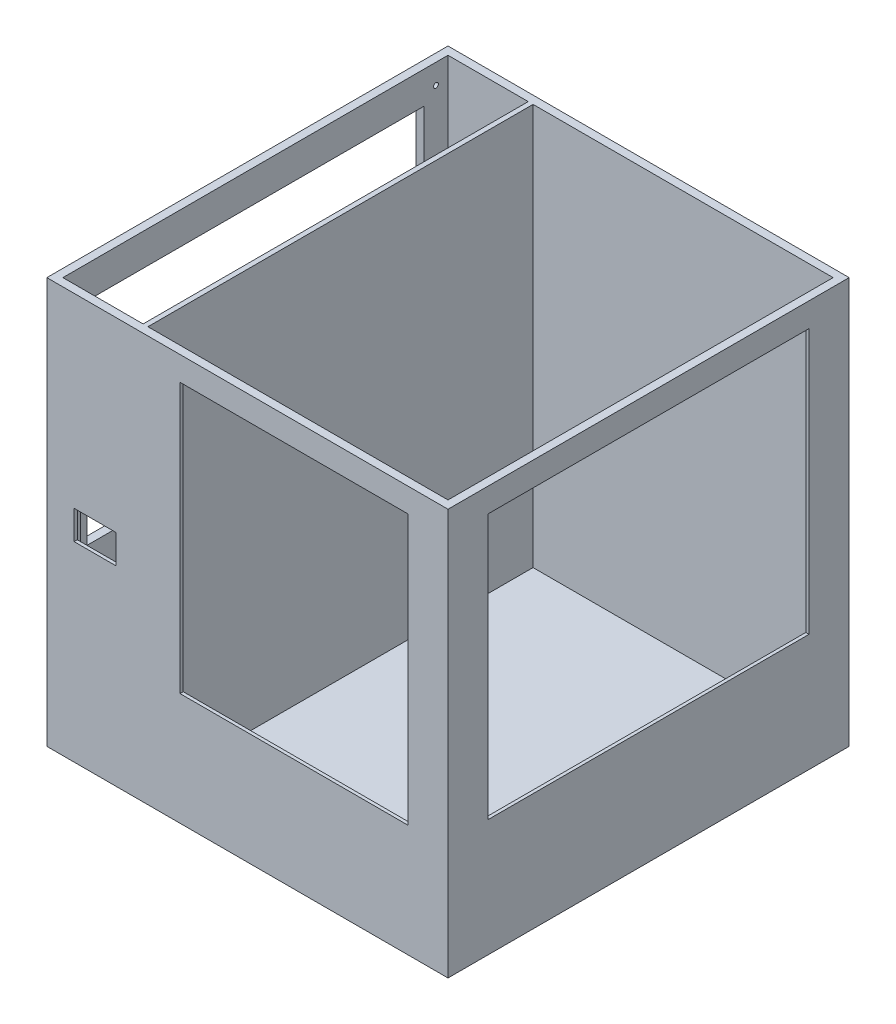
SolidWorks part; units mm, degrees
ref_plane "Спереди" through (0, 0, 0) normal (0, 0, 1) x (1, 0, 0)
ref_plane "Сверху" through (0, 0, 0) normal (0, 1, 0) x (1, 0, 0)
ref_plane "Справа" through (0, 0, 0) normal (1, 0, 0) x (0, 0, -1)
sketch "Эскиз1" plane through (0, 0, 0) normal (0, 1, 0) x (1, 0, 0)
  line L1 (-125, -125) -> (125, -125)
  line L2 (-125, -125) -> (-125, 125)
  line L3 (-125, 125) -> (125, 125)
  line L4 (125, -125) -> (125, 125)
  line L5 (-125, -125) -> (125, 125) construction
  line L6 (-125, 125) -> (125, -125) construction
  point P0 (0, 0)
  dimension "D1" = 250
  dimension "D2" = 250
extrude "Бобышка-Вытянуть1" add sketch "Эскиз1" along normal blind 3
sketch "Эскиз2" plane through (0, 3, 0) normal (0, 1, 0) x (1, 0, 0)
  line L1 (-125, -125) -> (125, -125)
  line L2 (-125, -125) -> (-125, 125)
  line L3 (-125, 125) -> (125, 125)
  line L4 (125, -125) -> (125, 125)
  line L5 (-125, -125) -> (125, 125) construction
  line L6 (-125, 125) -> (125, -125) construction
  line L7 (-120, -120) -> (120, -120)
  line L8 (-120, -120) -> (-120, 120)
  line L9 (-120, 120) -> (120, 120)
  line L10 (120, -120) -> (120, 120)
  line L11 (-120, -120) -> (120, 120) construction
  line L12 (-120, 120) -> (120, -120) construction
  point P0 (0, 0)
  point P6 (0, 0)
  dimension "D1" = 250
  dimension "D2" = 250
  dimension "D3" = 240
  dimension "D4" = 240
extrude "Бобышка-Вытянуть2" add sketch "Эскиз2" along normal blind 250
sketch "Эскиз3" plane through (0, 3, 0) normal (0, 1, 0) x (1, 0, 0)
  line L0 (120, 120) -> (-120, 120) construction
  line L1 (-70, 120) -> (-67, 120)
  line L2 (-70, 120) -> (-70, -120)
  line L3 (-70, -120) -> (-67, -120)
  line L4 (-67, 120) -> (-67, -120)
  line L5 (-120, -120) -> (120, -120) construction
  line L6 (-120, 120) -> (-120, -120) construction
  dimension "D1" = 3
  dimension "D2" = 50
extrude "Бобышка-Вытянуть3" add sketch "Эскиз3" along normal blind 250
sketch "Эскиз8" plane through (125, 0, 0) normal (1, 0, 0) x (0, 0, -1)
  line L0 (-125, 3) -> (125, 3) construction
  line L1 (-100, 73) -> (100, 73)
  line L2 (-100, 73) -> (-100, 238)
  line L3 (-100, 238) -> (100, 238)
  line L4 (100, 73) -> (100, 238)
  line L5 (-100, 73) -> (100, 238) construction
  line L6 (-100, 238) -> (100, 73) construction
  line L7 (-125, 253) -> (125, 253) construction
  line L8 (125, 253) -> (125, 0) construction
  point P0 (0, 155.5)
  dimension "D1" = 70
  dimension "D2" = 15
  dimension "D3" = 25
extrude "Вырез-Вытянуть4" cut sketch "Эскиз8" against normal blind 8
sketch "Эскиз9" plane through (120, 0, 0) normal (-1, 0, 0) x (0, 0, 1)
  line L0 (100, 73) -> (100, 238) construction
  line L1 (-110, 63) -> (110, 63)
  line L2 (-110, 63) -> (-110, 248)
  line L3 (-110, 248) -> (110, 248)
  line L4 (110, 63) -> (110, 248)
  line L5 (-110, 63) -> (110, 248) construction
  line L6 (-110, 248) -> (110, 63) construction
  line L7 (100, 238) -> (-100, 238) construction
  point P0 (0, 155.5)
  dimension "D1" = 10
  dimension "D2" = 10
extrude "Вырез-Вытянуть5" cut sketch "Эскиз9" against normal blind 3
sketch "Эскиз11" plane through (0, 0, 125) normal (0, 0, 1) x (1, 0, 0)
  line L0 (125, 253) -> (125, 0) construction
  line L1 (-42, 238) -> (100, 238)
  line L2 (-42, 238) -> (-42, 70)
  line L3 (-42, 70) -> (100, 70)
  line L4 (100, 238) -> (100, 70)
  line L5 (-125, 0) -> (125, 0) construction
  line L6 (-125, 253) -> (125, 253) construction
  line L7 (-125, 253) -> (-125, 0) construction
  dimension "D1" = 25
  dimension "D2" = 70
  dimension "D3" = 15
  dimension "D4" = 83
extrude "Вырез-Вытянуть6" cut sketch "Эскиз11" against normal blind 10
sketch "Эскиз12" plane through (0, 0, 120) normal (0, 0, -1) x (-1, 0, 0)
  line L0 (42, 238) -> (-100, 238) construction
  line L1 (-110, 248) -> (52, 248)
  line L2 (-110, 248) -> (-110, 60)
  line L3 (-110, 60) -> (52, 60)
  line L4 (52, 248) -> (52, 60)
  line L5 (42, 238) -> (42, 70) construction
  line L6 (-100, 238) -> (-100, 70) construction
  line L7 (42, 70) -> (-100, 70) construction
  dimension "D1" = 10
  dimension "D2" = 10
  dimension "D3" = 10
  dimension "D4" = 10
extrude "Вырез-Вытянуть7" cut sketch "Эскиз12" against normal blind 3
sketch "Эскиз16" plane through (0, 0, 125) normal (0, 0, 1) x (1, 0, 0)
  line L0 (-125, 253) -> (-125, 0) construction
  line L1 (-108, 119) -> (-82, 119)
  line L2 (-108, 119) -> (-108, 137)
  line L3 (-108, 137) -> (-82, 137)
  line L4 (-82, 119) -> (-82, 137)
  line L5 (-108, 119) -> (-82, 137) construction
  line L6 (-108, 137) -> (-82, 119) construction
  line L8 (-125, 0) -> (125, 0) construction
  point P0 (-95, 128)
  dimension "D1" = 26
  dimension "D2" = 18
  dimension "D3" = 30
  dimension "D4" = 128
extrude "Вырез-Вытянуть10" cut sketch "Эскиз16" against normal blind 5
sketch "Эскиз17" plane through (-125, 0, 0) normal (-1, 0, 0) x (0, 0, 1)
  line L0 (-125, 0) -> (125, 0) construction
  line L1 (101, 86) -> (110, 86)
  line L2 (101, 86) -> (101, 75)
  line L3 (101, 75) -> (110, 75)
  line L4 (110, 86) -> (110, 75)
  line L5 (66, 83) -> (81, 83)
  line L6 (66, 83) -> (66, 75)
  line L7 (66, 75) -> (81, 75)
  line L8 (81, 83) -> (81, 75)
  line L9 (125, 253) -> (125, 0) construction
  dimension "D1" = 11
  dimension "D2" = 9
  dimension "D3" = 8
  dimension "D4" = 15
  dimension "D5" = 75
  dimension "D6" = 75
  dimension "D7" = 20
  dimension "D8" = 15
extrude "Вырез-Вытянуть11" cut sketch "Эскиз17" against normal blind 10
sketch "Эскиз21" plane through (0, 0, 120) normal (0, 0, -1) x (-1, 0, 0)
  line L1 (81, 114) -> (109, 114)
  line L2 (81, 114) -> (81, 142)
  line L3 (81, 142) -> (109, 142)
  line L4 (109, 114) -> (109, 142)
  line L5 (81, 114) -> (109, 142) construction
  line L6 (81, 142) -> (109, 114) construction
  point P0 (95, 128)
  dimension "D1" = 28
  dimension "D2" = 28
extrude "Вырез-Вытянуть14" cut sketch "Эскиз21" against normal blind 3
sketch "Эскиз22" plane through (0, 0, -120) normal (0, 0, 1) x (1, 0, 0)
  line L0 (-120, 253) -> (-120, 3) construction
  line L5 (-120, 73) -> (-70, 73)
  line L6 (-120, 73) -> (-120, 70)
  line L7 (-120, 70) -> (-70, 70)
  line L8 (-70, 73) -> (-70, 70)
  line L9 (-70, 253) -> (-70, 3) construction
  line L10 (-70, 3) -> (-120, 3) construction
  dimension "D1" = 3
  dimension "D2" = 67
extrude "Бобышка-Вытянуть4" add sketch "Эскиз22" along normal blind 240
sketch "Эскиз24" plane through (-67, 0, 0) normal (1, 0, 0) x (0, 0, -1)
  line L0 (-120, 3) -> (120, 3) construction
  line L1 (120, 253) -> (120, 3) construction
  circle A0 centre (86.5, 53) radius 4
  dimension "D1" = 8
  dimension "D2" = 50
  dimension "D3" = 33.5
extrude "Вырез-Вытянуть15" cut sketch "Эскиз24" against normal blind 10
sketch "Эскиз25" plane through (-125, 0, 0) normal (-1, 0, 0) x (0, 0, 1)
  line L0 (-125, 253) -> (125, 253) construction
  line L1 (-105, 233) -> (105, 233)
  line L2 (-105, 233) -> (-105, 101)
  line L3 (-105, 101) -> (105, 101)
  line L4 (105, 233) -> (105, 101)
  line L5 (125, 253) -> (125, 0) construction
  line L6 (-125, 253) -> (-125, 0) construction
  line L7 (110, 86) -> (101, 86) construction
  dimension "D1" = 20
  dimension "D2" = 20
  dimension "D3" = 20
  dimension "D4" = 15
extrude "Вырез-Вытянуть16" cut sketch "Эскиз25" against normal blind 10
sketch "Эскиз26" plane through (-125, 0, 0) normal (-1, 0, 0) x (0, 0, 1)
  line L0 (-105, 101) -> (105, 101) construction
  line L1 (-105, 233) -> (-105, 101) construction
  line L2 (105, 101) -> (105, 233) construction
  line L3 (105, 233) -> (-105, 233) construction
  circle A0 centre (-112.5, 240.5) radius 1.5
  circle A1 centre (112.5, 240.5) radius 1.5
  circle A2 centre (112.5, 93.5) radius 1.5
  circle A3 centre (-112.5, 93.5) radius 1.5
  dimension "D1" = 3
  dimension "D2" = 3
  dimension "D3" = 3
  dimension "D4" = 3
  dimension "D5" = 7.5
  dimension "D6" = 7.5
  dimension "D7" = 7.5
  dimension "D8" = 7.5
  dimension "D9" = 7.5
  dimension "D10" = 7.5
  dimension "D11" = 7.5
  dimension "D12" = 7.5
extrude "Вырез-Вытянуть17" cut sketch "Эскиз26" against normal blind 10
